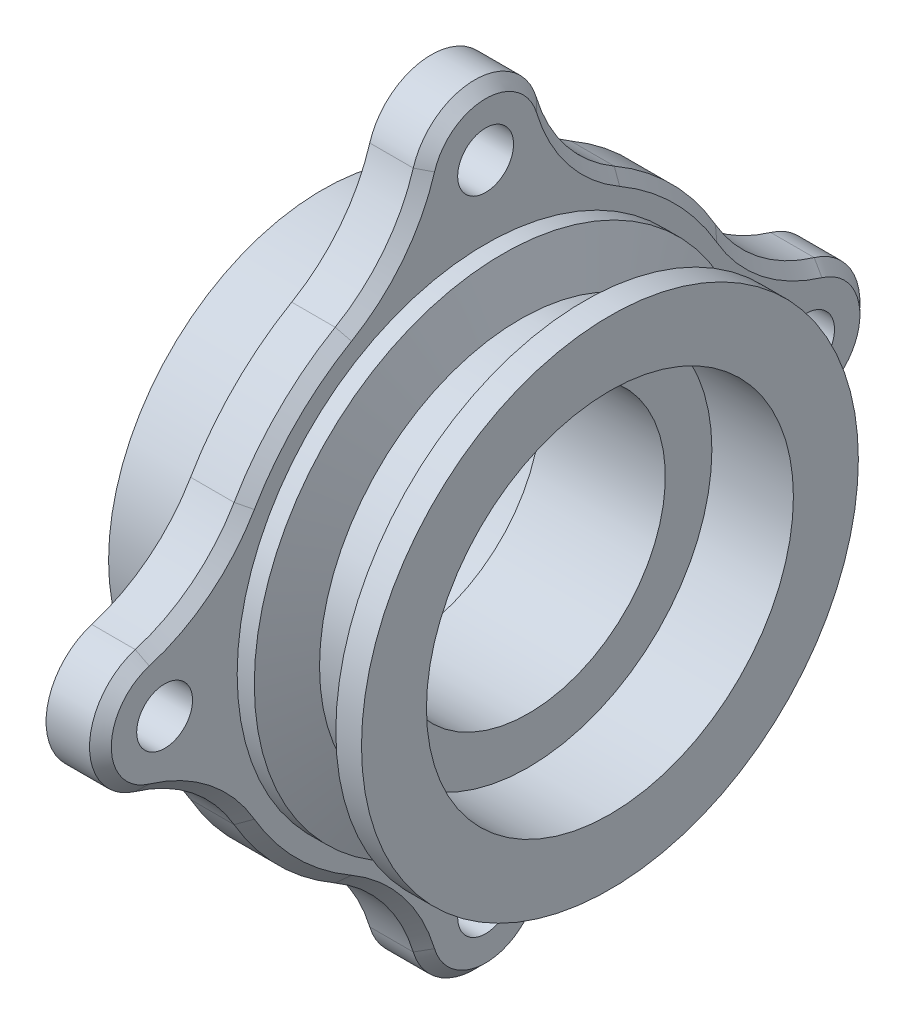
SolidWorks part; units mm, degrees
ref_plane "Front" through (0, 0, 0) normal (0, 0, 1) x (1, 0, 0)
ref_plane "Top" through (0, 0, 0) normal (0, 1, 0) x (1, 0, 0)
ref_plane "Right" through (0, 0, 0) normal (1, 0, 0) x (0, 0, -1)
sketch "Sketch1" plane through (0, 0, 0) normal (0, 0, 1) x (1, 0, 0)
  line L0 (-12.7, 25) -> (0, 25)
  line L1 (0, 25) -> (0, 45)
  line L2 (0, 45) -> (6.35, 45)
  line L3 (6.35, 45) -> (6.35, 29.0256)
  line L4 (6.35, 29.0256) -> (8.35, 29.0256)
  line L5 (8.35, 29.0256) -> (10.3839, 23.4376)
  line L6 (10.3839, 23.4376) -> (15.8411, 23.4376)
  line L7 (15.8411, 23.4376) -> (17.875, 29.0256)
  line L8 (17.875, 29.0256) -> (20.875, 29.0256)
  line L9 (20.875, 29.0256) -> (20.875, 21.4376)
  line L10 (0, 0) -> (27.6559, 0) construction
  line L11 (0, 35) -> (6.35, 35) construction
  line L12 (20.875, 21.4376) -> (11.35, 21.4376)
  line L13 (11.35, 21.4376) -> (11.35, 16)
  line L14 (11.35, 16) -> (-3.175, 16)
  line L15 (-3.175, 16) -> (-3.175, 21.4376)
  line L16 (-3.175, 21.4376) -> (-12.7, 21.4376)
  line L17 (-12.7, 21.4376) -> (-12.7, 25)
  line L18 (13.1125, 23.4376) -> (13.1125, 25.8182) construction
  line L19 (0, 39.7625) -> (6.35, 39.7625) construction
  line L20 (0, 30.2375) -> (6.35, 30.2375) construction
  point P16 (3.175, 35)
  point P17 (3.175, 45)
  point P29 (0, 0)
  point P30 (4.0401, 42.1031)
  point P31 (15.9126, 23.4376)
  point P32 (9.8439, 29.0256)
  point P33 (6.3292, 15.2669)
  point P34 (26.1582, 29.0256)
  point P35 (-2.3252, 16)
  dimension "D1" = 9.525
  dimension "D2" = 35
  dimension "D3" = 50
  dimension "D4" = 42.8752
  dimension "D5" = 5.588
  dimension "D6" = 9.525
  dimension "D7" = 2
  dimension "D8" = 40
  dimension "D9" = 9.525
  dimension "D10" = 9.525
  dimension "D11" = 3
  dimension "D12" = 2
  dimension "D13" = 6.35
  dimension "D14" = 32
  dimension "D15" = 12.7
  dimension "D16" = 90
revolve "Revolve1" add sketch "Sketch1" angle 360 about L10
hole_wizard "5/16-18 Tapped Hole1" positions "Sketch2" profile "Sketch4" tap size "5/16-18" standard "ANSI Inch"
sketch "Sketch2" plane through (0, 0, 0) normal (-1, 0, 0) x (0, 0, 1)
  circle A0 centre (0, 0) radius 37.5 construction
  point P5 (0, 37.5)
  point P14 (37.5, 0)
  point P15 (0, -37.5)
  point P16 (-37.5, 0)
  point P18 (-37.5, 0)
  dimension "D1" = 75
  dimension "D2" = 4
sketch "Sketch4" plane through (0, 0, -37.5) normal (0, 1, 0) x (0, 0, 1)
  line L0 (0, 0) -> (0, 56.0711)
  line L1 (0, 56.0711) -> (3.2639, 54.11)
  line L2 (3.2639, 54.11) -> (3.2639, 0)
  line L5 (3.2639, 0) -> (0, 0)
  line L10 (0, 56.0711) -> (-3.2639, 54.11) construction
  line L11 (0, -6.35) -> (0, 107.95) construction
  dimension "Tap Drill Dia." = 6.5278
  dimension "Tap Drill Depth" = 54.11
  dimension "Drill Angle" = 118
cosmetic thread "Hole Thread1" parameters "D1"=15.88, "D2"=7.9375
cosmetic thread "Hole Thread2" parameters "D1"=15.88, "D2"=7.9375
cosmetic thread "Hole Thread3" parameters "D1"=15.88, "D2"=7.9375
cosmetic thread "Hole Thread4" parameters "D1"=15.88, "D2"=7.9375
sketch "Sketch5" plane through (6.35, 0, 0) normal (1, 0, 0) x (0, 0, -1)
  arc A1 (5.1875, 32.0833) -> (-5.1875, 32.0833) centre (0, 37.5) ccw
  arc A2 (32.0833, -5.1875) -> (32.0833, 5.1875) centre (37.5, 0) ccw
  arc A3 (-5.1875, -32.0833) -> (5.1875, -32.0833) centre (0, -37.5) ccw
  arc A4 (-32.0833, 5.1875) -> (-32.0833, -5.1875) centre (-37.5, 0) ccw
  circle A5 centre (0, 0) radius 45 construction
  circle A9 centre (0, 0) radius 45
  circle A10 centre (0, 0) radius 32.5
  circle A11 centre (37.5, 0) radius 3.2639 construction
  point P1 (0, 37.5)
  point P3 (0, 37.5)
  point P16 (0, 0)
  point P21 (37.5, 2.1835)
  circle M8 centre (0, 0) radius 45
  dimension "D1" = 4
  dimension "D2" = 65
extrude "Cut-Extrude1" cut sketch "Sketch5" against normal through all contours A1 A4 M8 | A4 A3 M8 | A3 A2 M8 | A2 A1 M8 region at (6.35, 25.9747, -25.9747) region at (6.35, 25.9747, 25.9747) region at (6.35, -25.9747, -25.9747) region at (6.35, -25.9747, 25.9747)
fillet "Fillet1" radius 20 8 edges at (3.175, 5.1875, 32.0833) (3.175, -5.1875, 32.0833) (3.175, -32.0833, 5.1875) (3.175, -32.0833, -5.1875) (3.175, -5.1875, -32.0833) (3.175, 5.1875, -32.0833) (3.175, 32.0833, -5.1875) (3.175, 32.0833, 5.1875)
chamfer "Chamfer1" distance 1.27 angle 45 16 edges at (6.35, -33.018, 10.6428) (6.35, -45, 0) (6.35, -22.981, 22.981) (6.35, -33.018, -10.6428) (6.35, -10.6428, 33.018) (6.35, -22.981, -22.981) (6.35, 0, 45) (6.35, -10.6428, -33.018) (6.35, 10.6428, 33.018) (6.35, 0, -45) (6.35, 22.981, 22.981) (6.35, 10.6428, -33.018) (6.35, 33.018, 10.6428) (6.35, 22.981, -22.981) (6.35, 45, 0) (6.35, 33.018, -10.6428)
